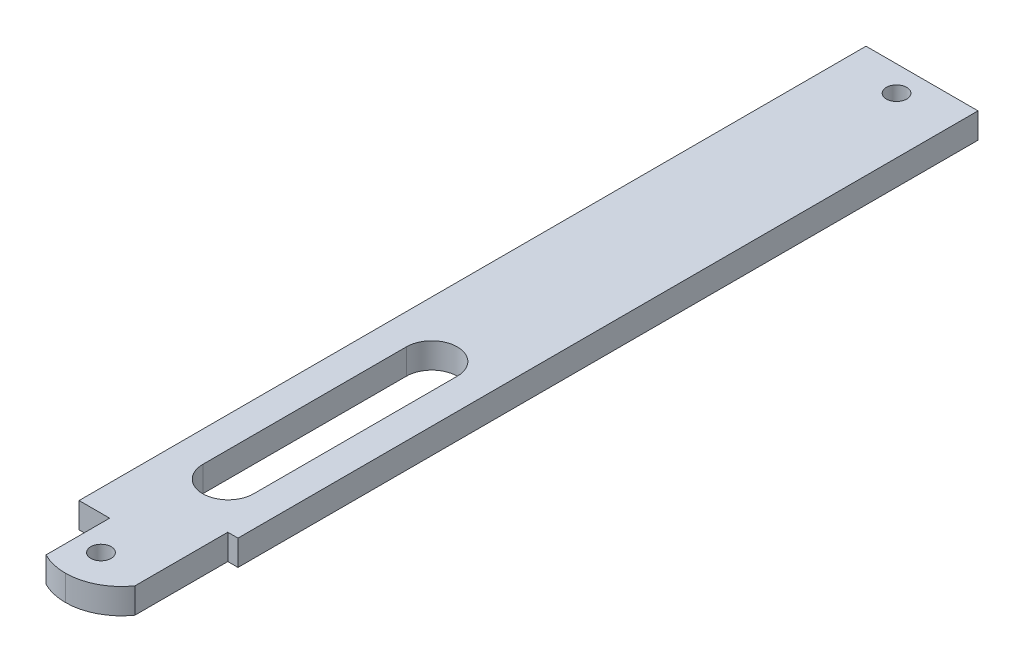
SolidWorks part; units mm, degrees
ref_plane "Front" through (0, 0, 0) normal (0, 0, 1) x (1, 0, 0)
ref_plane "Top" through (0, 0, 0) normal (0, 1, 0) x (1, 0, 0)
ref_plane "Right" through (0, 0, 0) normal (1, 0, 0) x (0, 0, -1)
sketch "Sketch1" plane through (0, 0, 0) normal (0, 1, 0) x (1, 0, 0)
  line L0 (11, 166.3) -> (11, 161.3)
  line L1 (0, 0) -> (22, 0)
  line L2 (0, 0) -> (0, 166.3)
  line L3 (0, 166.3) -> (22, 166.3)
  line L4 (22, 0) -> (22, 166.3)
  line L5 (5, 161.3) -> (17, 161.3)
  line L6 (0, 83.15) -> (22, 83.15)
  line L7 (17, 5) -> (5, 5)
  circle A0 centre (5, 161.3) radius 1.5
  circle A1 centre (17, 161.3) radius 1.5
  circle A2 centre (17, 5) radius 1.5
  circle A3 centre (5, 5) radius 1.5
  circle A4 centre (11, 5) radius 2
  circle A5 centre (11, 161.3) radius 2
  point P10 (11, 161.3)
  dimension "D1" = 166.3
  dimension "D2" = 22
  dimension "D3" = 12
extrude "Boss-Extrude1" add sketch "Sketch1" along normal blind 5 contours A1 A0 L3 L2 L6 L4 | L6 L2 L1 L4 A2 A3 | A2 | A3 | A1 | A0 region at (11, 0, -124.1832) region at (11, 0, -42.1168)
sketch "Sketch2" plane through (0, 0, 0) normal (0, -1, 0) x (-1, 0, 0)
  line L0 (-11, 0) -> (-11, 30)
  line L1 (0, 0) -> (-22, 0) construction
  line L2 (-11, 30) -> (-11, 70)
  line L3 (-11, 30) -> (-11, 70) construction
  line L4 (-16, 30) -> (-16, 70)
  line L5 (-6, 30) -> (-6, 70)
  arc A0 (-16, 30) -> (-6, 30) centre (-11, 30) ccw
  arc A1 (-6, 70) -> (-16, 70) centre (-11, 70) ccw
  point P5 (-11, 50)
  dimension "D3" = 5
  dimension "D1" = 30
  dimension "D2" = 40
extrude "Cut-Extrude1" cut sketch "Sketch2" against normal blind 5 contours L5 A1 L4 A0 region at (15.4901, 0, -50)
sketch "Sketch3" plane through (0, 0, 0) normal (0, 0, 1) x (1, 0, 0)
  line L1 (22, 0) -> (0, 0)
  line L2 (22, 0) -> (22, 5)
  line L3 (22, 5) -> (0, 5)
  line L4 (0, 0) -> (0, 5)
extrude "Boss-Extrude2" add sketch "Sketch3" along normal blind 6
sketch "Sketch4" plane through (0, 0, 6) normal (0, 0, 1) x (1, 0, 0)
  line L1 (22, 0) -> (0, 0)
  line L2 (22, 0) -> (22, 5)
  line L3 (22, 5) -> (0, 5)
  line L4 (0, 0) -> (0, 5)
extrude "Cut-Extrude2" cut sketch "Sketch4" against normal blind 4
fillet "Fillet2" radius 11 2 edges at (0, 2.5, 2) (22, 2.5, 2)
sketch "Sketch5" plane through (0, 0, 0) normal (-1, 0, 0) x (0, 0, 1)
  line L0 (-9, 0) -> (-166.3, 0) construction
  line L1 (-11.6999, 0) -> (7.5806, 0)
  line L2 (-11.6999, 0) -> (-11.6999, 5)
  line L3 (-11.6999, 5) -> (7.5806, 5)
  line L4 (7.5806, 0) -> (7.5806, 5)
extrude "Cut-Extrude3" cut sketch "Sketch5" against normal blind 6
sketch "Sketch7" plane through (22, 0, 0) normal (1, 0, 0) x (0, 0, -1)
  line L0 (9, 5) -> (166.3, 5) construction
  line L1 (20.9171, 5) -> (-8.454, 5)
  line L2 (20.9171, 5) -> (20.9171, 0)
  line L3 (20.9171, 0) -> (-8.454, 0)
  line L4 (-8.454, 5) -> (-8.454, 0)
extrude "Cut-Extrude4" cut sketch "Sketch7" against normal blind 2
